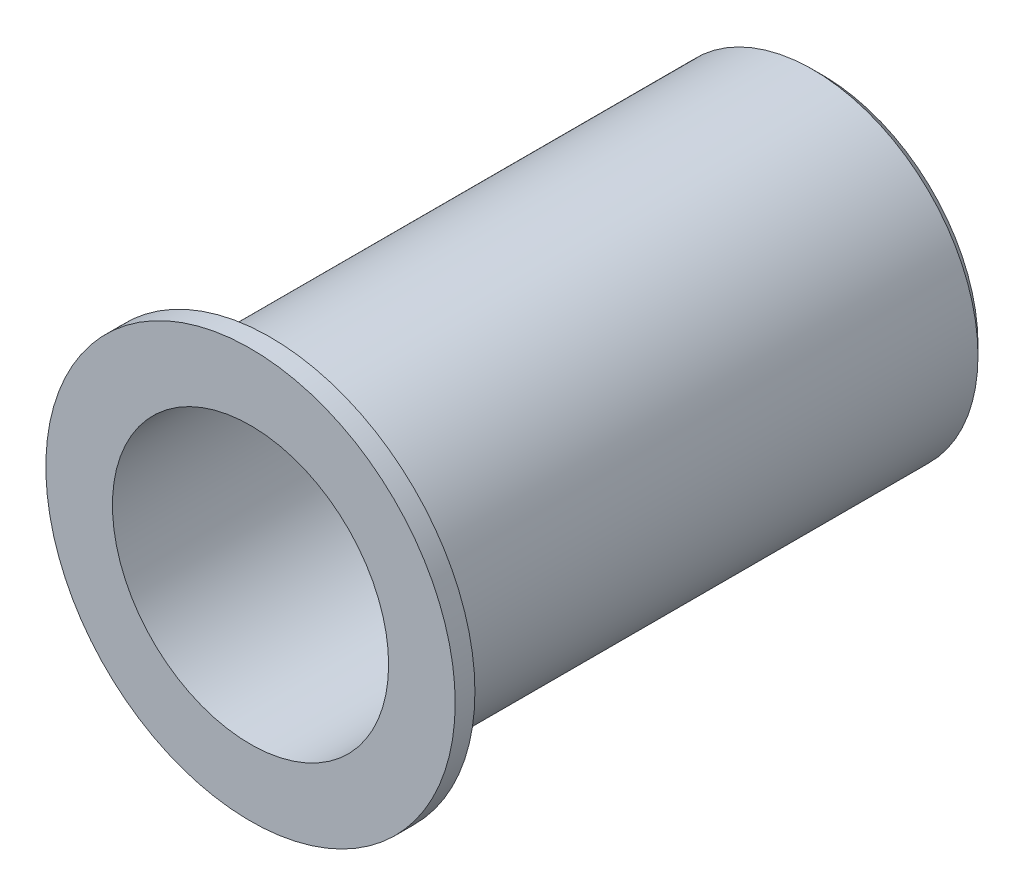
SolidWorks part; units mm, degrees
ref_plane "前视基准面" through (0, 0, 0) normal (0, 0, 1) x (1, 0, 0)
ref_plane "上视基准面" through (0, 0, 0) normal (0, 1, 0) x (1, 0, 0)
ref_plane "右视基准面" through (0, 0, 0) normal (1, 0, 0) x (0, 0, -1)
sketch "草图1" plane through (0, 0, 0) normal (0, 0, 1) x (1, 0, 0)
  circle A0 centre (0, 0) radius 8.375
  dimension "D1" = 16.75
extrude "凸台-拉伸1" add sketch "草图1" along normal blind 28
sketch "草图2" plane through (0, 0, 28) normal (0, 0, 1) x (1, 0, 0)
  circle A0 centre (0, 0) radius 7
extrude "切除-拉伸3" cut sketch "草图2" against normal blind 23
sketch "草图3" plane through (0, 0, 0) normal (0, 0, -1) x (-1, 0, 0)
  circle A0 centre (0, 0) radius 7 construction
  circle A1 centre (0, 0) radius 5
  circle A3 centre (0, 0) radius 7
  point P2 (0, 5)
  point P7 (4.3301, -2.5)
  point P8 (-4.3301, -2.5)
  point P9 (0, 0)
  dimension "D1" = 10
  dimension "D2" = 3
hole_wizard "M4 螺纹孔1" positions "草图8" profile "草图9" tap size "M4" standard "GB" end condition through all
sketch "草图8" plane through (0, 0, 0) normal (0, 0, -1) x (-1, 0, 0)
  point P0 (0, 5)
  point P3 (0, 0)
  point P6 (-4.3301, -2.5)
  point P9 (4.3301, -2.5)
sketch "草图9" plane through (0, 5, 0) normal (1, 0, 0) x (0, 1, 0)
  line L0 (0, 0) -> (0, 28)
  line L1 (0, 28) -> (1.65, 28)
  line L2 (1.65, 28) -> (1.65, 0)
  line L5 (1.65, 0) -> (0, 0)
  line L11 (0, -6.35) -> (0, 107.95) construction
  dimension "通孔螺纹孔钻头直径" = 3.3
  dimension "通孔螺纹孔钻头深度" = 28
cosmetic thread "孔螺蚊线5" parameters "D2"=4
cosmetic thread "孔螺蚊线6" parameters "D2"=4
cosmetic thread "孔螺蚊线7" parameters "D2"=4
cosmetic thread "孔螺蚊线8" parameters "D2"=4
sketch "草图10" plane through (0, 0, 28) normal (0, 0, 1) x (1, 0, 0)
  circle A0 centre (0, 0) radius 10.375
  circle A1 centre (0, 0) radius 8.375
  circle A2 centre (0, 0) radius 8.375
  circle A3 centre (0, 0) radius 7 construction
  circle A4 centre (0, 0) radius 7
  circle M2 centre (0, 0) radius 7
  circle M3 centre (0, 0) radius 8.375
  dimension "D1" = 0
  dimension "D2" = 2
extrude "凸台-拉伸4" add sketch "草图10" along normal blind 1 contours A0 M3 | M3 M2 region at (-10.0816, 0, 28) region at (-8.1381, 0, 28)
chamfer "倒角1" distance 0.5 angle 45 1 edges at (8.375, 0, 0)
